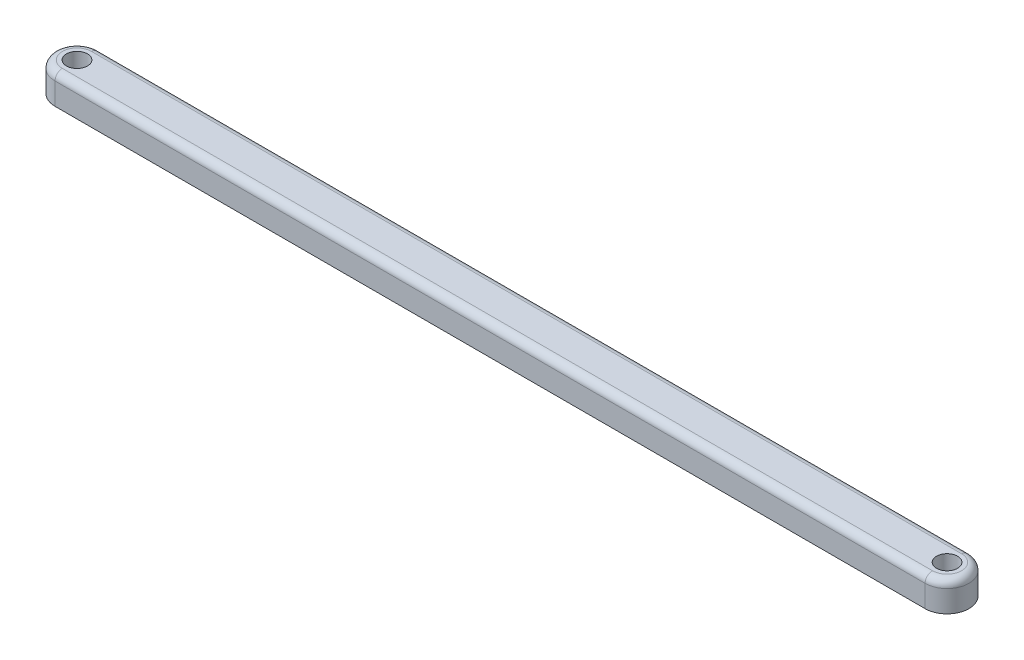
SolidWorks part; units mm, degrees
ref_plane "Front Plane" through (0, 0, 0) normal (0, 0, 1) x (1, 0, 0)
ref_plane "Top Plane" through (0, 0, 0) normal (0, 1, 0) x (1, 0, 0)
ref_plane "Right Plane" through (0, 0, 0) normal (1, 0, 0) x (0, 0, -1)
sketch "Sketch1" plane through (0, 0, 0) normal (0, 1, 0) x (1, 0, 0)
  line L0 (0, 0) -> (188.9125, 0) construction
  line L1 (0, 4.7625) -> (188.9125, 4.7625)
  line L2 (0, -4.7625) -> (188.9125, -4.7625)
  arc A0 (0, 4.7625) -> (0, -4.7625) centre (0, 0) ccw
  arc A1 (188.9125, -4.7625) -> (188.9125, 4.7625) centre (188.9125, 0) ccw
  point P3 (94.4562, 0)
  dimension "D1" = 188.9125
  dimension "D2" = 9.525
extrude "Boss-Extrude1" add sketch "Sketch1" along normal mid plane 6.35
sketch "Sketch2" plane through (0, 3.175, 0) normal (0, 1, 0) x (1, 0, 0)
  circle A0 centre (0, 0) radius 2.286
  circle A1 centre (188.9125, 0) radius 2.286
  dimension "D1" = 4.572
extrude "Cut-Extrude1" cut sketch "Sketch2" against normal through all
fillet "Fillet1" radius 1.5875 4 edges at (193.675, 3.175, 0) (94.4562, 3.175, 4.7625) (-4.7625, 3.175, 0) (94.4562, 3.175, -4.7625)
